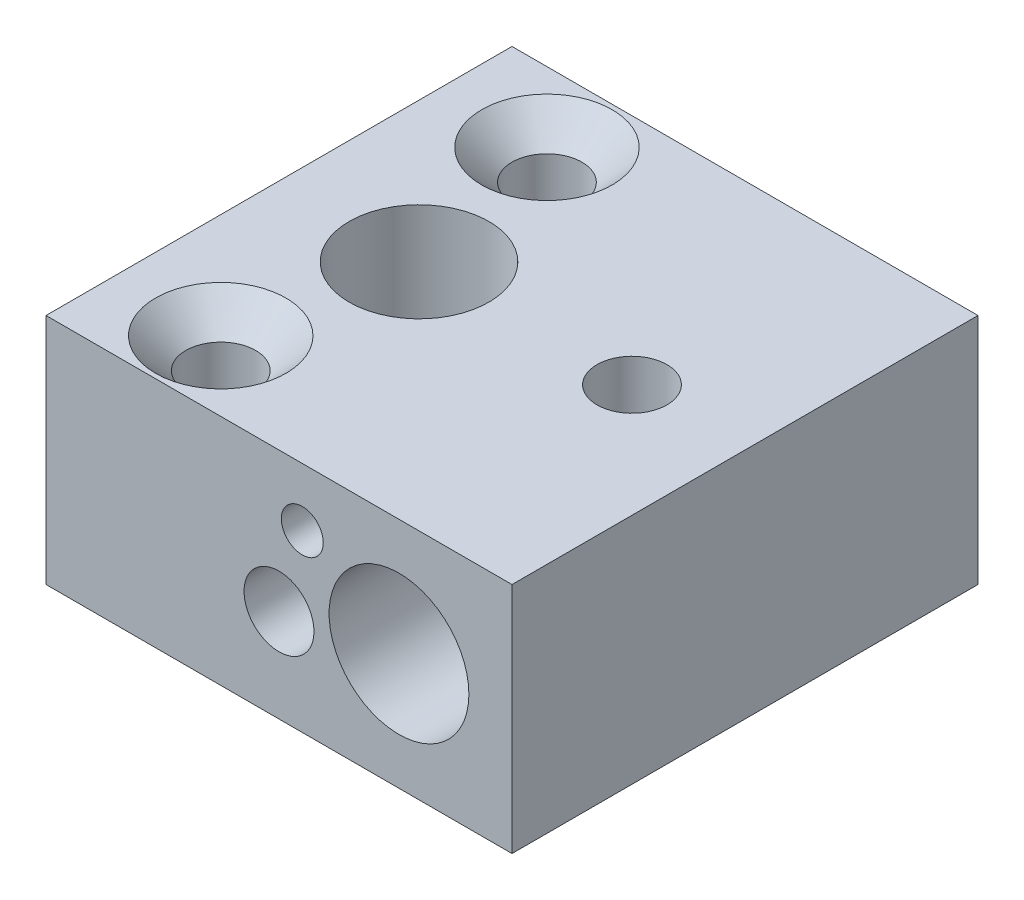
SolidWorks part; units mm, degrees
ref_plane "Płaszczyzna przednia" through (0, 0, 0) normal (0, 0, 1) x (1, 0, 0)
ref_plane "Płaszczyzna górna" through (0, 0, 0) normal (0, 1, 0) x (1, 0, 0)
ref_plane "Płaszczyzna prawa" through (0, 0, 0) normal (1, 0, 0) x (0, 0, -1)
sketch "Sketch1" plane through (0, 0, 0) normal (0, 1, 0) x (1, 0, 0)
  line L1 (0, 0) -> (20, 0)
  line L2 (0, 0) -> (0, 20)
  line L3 (0, 20) -> (20, 20)
  line L4 (20, 0) -> (20, 20)
  dimension "D1" = 20
  dimension "D2" = 20
extrude "Boss-Extrude1" add sketch "Sketch1" along normal blind 10
hole_wizard "Ø6.0mm Dowel Hole2" positions "Sketch2" profile "Sketch3" hole size "Ø6.0" standard "ANSI Metric" end condition through all
sketch "Sketch2" plane through (0, 10, 0) normal (0, 1, 0) x (1, 0, 0)
  line L0 (0, 20) -> (0, 0) construction
  line L2 (0, 0) -> (20, 0) construction
  point P0 (6.01, 10)
  point P9 (3.947, 0)
  dimension "D1" = 6.01
  dimension "D2" = 10
sketch "Sketch3" plane through (6.01, 10, -10) normal (1, 0, 0) x (0, 0, 1)
  line L0 (0, 0) -> (0, 10)
  line L1 (0, 10) -> (3, 10)
  line L2 (3, 10) -> (3, 0)
  line L5 (3, 0) -> (0, 0)
  line L11 (0, -6.35) -> (0, 107.95) construction
  dimension "Thru Hole Dia." = 6
  dimension "Thru Hole Depth" = 10
hole_wizard "CSK for M3 Flat Head Machine Screw1" positions "Sketch4" profile "Sketch5" countersink size "M3" standard "ANSI Metric"
sketch "Sketch4" plane through (0, 10, 0) normal (0, 1, 0) x (1, 0, 0)
  line L0 (0, 20) -> (0, 0) construction
  line L1 (0, 0) -> (20, 0) construction
  point P0 (4.5, 3)
  point P2 (4.5, 17)
  dimension "D1" = 4.5
  dimension "D2" = 14
  dimension "D3" = 3
sketch "Sketch5" plane through (4.5, 10, -3) normal (1, 0, 0) x (0, 0, 1)
  line L0 (0, 0) -> (0, 6.9013)
  line L1 (0, 6.9013) -> (1.5, 6)
  line L2 (1.5, 6) -> (1.5, 1.3)
  line L3 (1.5, 1.3) -> (2.8, 0)
  line L5 (2.8, 0) -> (0, 0)
  line L6 (-1.5, 1.3) -> (-2.8, 0) construction
  line L10 (0, 6.9013) -> (-1.5, 6) construction
  line L11 (0, -6.35) -> (0, 107.95) construction
  dimension "Hole Dia." = 3
  dimension "Hole Depth" = 6
  dimension "Near C'Sink Dia." = 5.6
  dimension "Near C'Sink Angle" = 90
  dimension "Drill Angle" = 118
hole_wizard "Ø6.0mm Dowel Hole3" positions "Sketch6" profile "Sketch8" hole size "Ø6.0" standard "ANSI Metric" end condition through all
sketch "Sketch6" plane through (0, 0, 0) normal (0, 0, 1) x (1, 0, 0)
  line L0 (0, 10) -> (20, 10) construction
  line L2 (20, 10) -> (20, 0) construction
  point P0 (15.15, 5)
  point P9 (20, 5.7135)
  dimension "D1" = 5
  dimension "D2" = 4.85
sketch "Sketch8" plane through (15.15, 5, 0) normal (1, 0, 0) x (0, -1, 0)
  line L0 (0, 0) -> (0, 20)
  line L1 (0, 20) -> (3, 20)
  line L2 (3, 20) -> (3, 0)
  line L5 (3, 0) -> (0, 0)
  line L11 (0, -6.35) -> (0, 107.95) construction
  dimension "Thru Hole Dia." = 6
  dimension "Thru Hole Depth" = 20
hole_wizard "Ø3.0mm Dowel Hole1" positions "Sketch9" profile "Sketch10" hole size "Ø3.0" standard "ANSI Metric" end condition up to next
sketch "Sketch9" plane through (0, 10, 0) normal (0, 1, 0) x (1, 0, 0)
  line L0 (20, 0) -> (20, 20) construction
  line L1 (0, 0) -> (20, 0) construction
  point P0 (15.15, 10)
  point P7 (0, 0)
  dimension "D1" = 4.85
  dimension "D2" = 10
sketch "Sketch10" plane through (15.15, 10, -10) normal (1, 0, 0) x (0, 0, 1)
  line L0 (0, 0) -> (0, 2)
  line L1 (0, 2) -> (1.5, 2)
  line L2 (1.5, 2) -> (1.5, 0)
  line L5 (1.5, 0) -> (0, 0)
  line L11 (0, -6.35) -> (0, 107.95) construction
  dimension "Thru Hole Dia." = 3
  dimension "Thru Hole Depth" = 2
hole_wizard "Ø3.0mm Dowel Hole2" positions "Sketch13" profile "Sketch14" hole size "Ø3.0" standard "ANSI Metric"
sketch "Sketch13" plane through (0, 0, 0) normal (0, 0, 1) x (1, 0, 0)
  line L0 (20, 10) -> (20, 0) construction
  circle A0 centre (15.15, 5) radius 3 construction
  point P0 (10, 4)
  dimension "D1" = 1
  dimension "D2" = 10
sketch "Sketch14" plane through (10, 4, 0) normal (1, 0, 0) x (0, -1, 0)
  line L0 (0, 0) -> (0, 6.9013)
  line L1 (0, 6.9013) -> (1.5, 6)
  line L2 (1.5, 6) -> (1.5, 0)
  line L5 (1.5, 0) -> (0, 0)
  line L10 (0, 6.9013) -> (-1.5, 6) construction
  line L11 (0, -6.35) -> (0, 107.95) construction
  dimension "Hole Dia." = 3
  dimension "Hole Depth" = 6
  dimension "Drill Angle" = 118
hole_wizard "Ø1.5mm Dowel Hole1" positions "Sketch15" profile "Sketch16" hole size "Ø1.5" standard "ANSI Metric"
sketch "Sketch15" plane through (0, 0, 0) normal (0, 0, 1) x (1, 0, 0)
  line L0 (20, 10) -> (20, 0) construction
  line L1 (0, 10) -> (20, 10) construction
  point P0 (11, 7.5)
  point P3 (0, 0)
  dimension "D1" = 9
  dimension "D2" = 2.5
sketch "Sketch16" plane through (11, 7.5, 0) normal (1, 0, 0) x (0, -1, 0)
  line L0 (0, 0) -> (0, 4.5408)
  line L1 (0, 4.5408) -> (0.9, 4)
  line L2 (0.9, 4) -> (0.9, 0)
  line L5 (0.9, 0) -> (0, 0)
  line L10 (0, 4.5408) -> (-0.9, 4) construction
  line L11 (0, -6.35) -> (0, 107.95) construction
  dimension "Hole Dia." = 1.8
  dimension "Hole Depth" = 4
  dimension "Drill Angle" = 118
